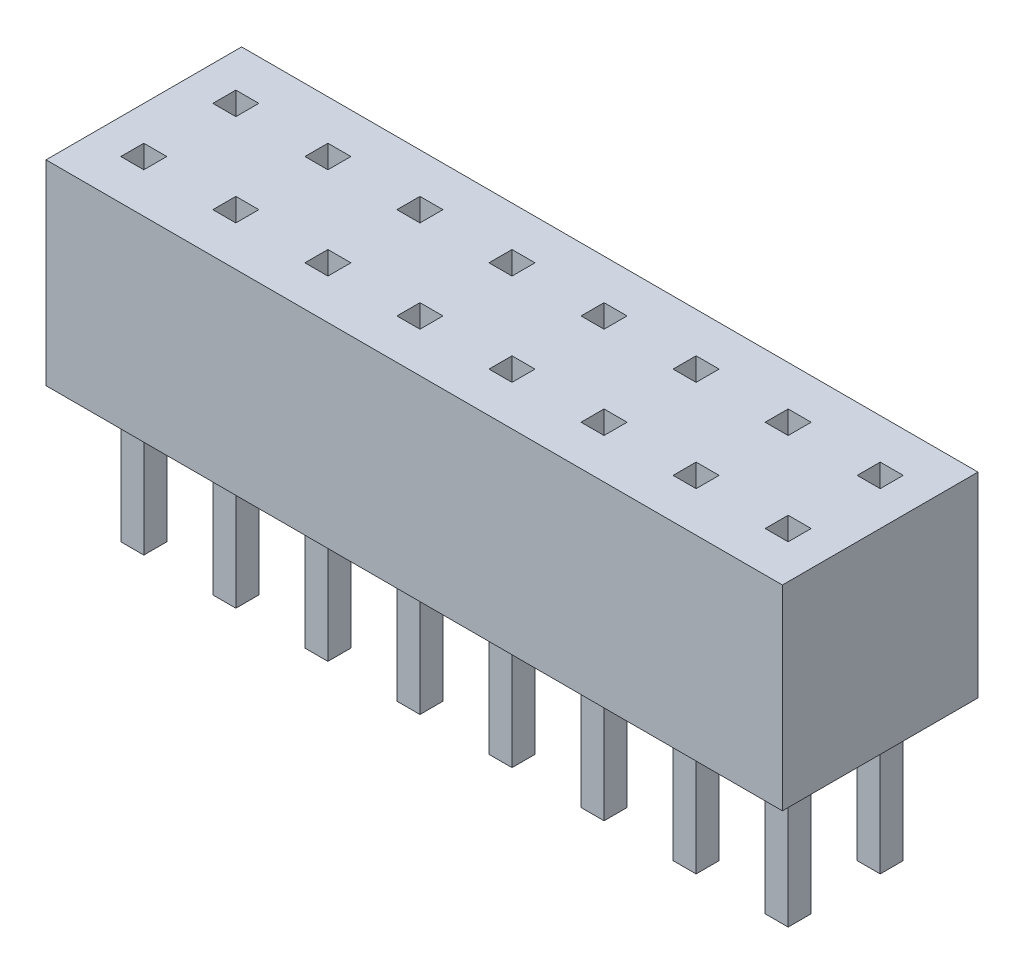
SolidWorks part; units mm, degrees
ref_plane "Front Plane" through (0, 0, 0) normal (0, 0, 1) x (1, 0, 0)
ref_plane "Top Plane" through (0, 0, 0) normal (0, 1, 0) x (1, 0, 0)
ref_plane "Right Plane" through (0, 0, 0) normal (1, 0, 0) x (0, 0, -1)
sketch "Sketch1" plane through (0, 0, 0) normal (0, 1, 0) x (1, 0, 0)
  line L1 (0, 0) -> (16, 0)
  line L2 (0, 0) -> (0, -4.25)
  line L3 (0, -4.25) -> (16, -4.25)
  line L4 (16, 0) -> (16, -4.25)
extrude "Boss-Extrude1" add sketch "Sketch1" along normal blind 4.25
sketch "Sketch3" plane through (0, 0, 0) normal (0, -1, 0) x (1, 0, 0)
  line L0 (2.75, 0.875) -> (3.25, 0.875)
  line L1 (0.75, 0.875) -> (1.25, 0.875)
  line L2 (0.75, 0.875) -> (0.75, 1.375)
  line L3 (0.75, 1.375) -> (1.25, 1.375)
  line L4 (1.25, 0.875) -> (1.25, 1.375)
  line L5 (2.75, 0.875) -> (2.75, 1.375)
  line L6 (2.75, 1.375) -> (3.25, 1.375)
  line L7 (3.25, 0.875) -> (3.25, 1.375)
  line L8 (4.75, 0.875) -> (5.25, 0.875)
  line L9 (4.75, 0.875) -> (4.75, 1.375)
  line L10 (4.75, 1.375) -> (5.25, 1.375)
  line L11 (5.25, 0.875) -> (5.25, 1.375)
  line L12 (6.75, 0.875) -> (7.25, 0.875)
  line L13 (6.75, 0.875) -> (6.75, 1.375)
  line L14 (6.75, 1.375) -> (7.25, 1.375)
  line L15 (7.25, 0.875) -> (7.25, 1.375)
  line L16 (8.75, 0.875) -> (9.25, 0.875)
  line L17 (8.75, 0.875) -> (8.75, 1.375)
  line L18 (8.75, 1.375) -> (9.25, 1.375)
  line L19 (9.25, 0.875) -> (9.25, 1.375)
  line L20 (10.75, 0.875) -> (11.25, 0.875)
  line L21 (10.75, 0.875) -> (10.75, 1.375)
  line L22 (10.75, 1.375) -> (11.25, 1.375)
  line L23 (11.25, 0.875) -> (11.25, 1.375)
  line L24 (12.75, 0.875) -> (13.25, 0.875)
  line L25 (12.75, 0.875) -> (12.75, 1.375)
  line L26 (12.75, 1.375) -> (13.25, 1.375)
  line L27 (13.25, 0.875) -> (13.25, 1.375)
  line L28 (14.75, 0.875) -> (15.25, 0.875)
  line L29 (14.75, 0.875) -> (14.75, 1.375)
  line L30 (14.75, 1.375) -> (15.25, 1.375)
  line L31 (15.25, 0.875) -> (15.25, 1.375)
  line L72 (0.75, 2.875) -> (1.25, 2.875)
  line L73 (0.75, 2.875) -> (0.75, 3.375)
  line L74 (0.75, 3.375) -> (1.25, 3.375)
  line L75 (1.25, 2.875) -> (1.25, 3.375)
  line L76 (2.75, 2.875) -> (3.25, 2.875)
  line L77 (2.75, 2.875) -> (2.75, 3.375)
  line L78 (2.75, 3.375) -> (3.25, 3.375)
  line L79 (3.25, 2.875) -> (3.25, 3.375)
  line L80 (4.75, 2.875) -> (5.25, 2.875)
  line L81 (4.75, 2.875) -> (4.75, 3.375)
  line L82 (4.75, 3.375) -> (5.25, 3.375)
  line L83 (5.25, 2.875) -> (5.25, 3.375)
  line L84 (6.75, 2.875) -> (7.25, 2.875)
  line L85 (6.75, 2.875) -> (6.75, 3.375)
  line L86 (6.75, 3.375) -> (7.25, 3.375)
  line L87 (7.25, 2.875) -> (7.25, 3.375)
  line L88 (8.75, 2.875) -> (9.25, 2.875)
  line L89 (8.75, 2.875) -> (8.75, 3.375)
  line L90 (8.75, 3.375) -> (9.25, 3.375)
  line L91 (9.25, 2.875) -> (9.25, 3.375)
  line L92 (10.75, 2.875) -> (11.25, 2.875)
  line L93 (10.75, 2.875) -> (10.75, 3.375)
  line L94 (10.75, 3.375) -> (11.25, 3.375)
  line L95 (11.25, 2.875) -> (11.25, 3.375)
  line L96 (12.75, 2.875) -> (13.25, 2.875)
  line L97 (12.75, 2.875) -> (12.75, 3.375)
  line L98 (12.75, 3.375) -> (13.25, 3.375)
  line L99 (13.25, 2.875) -> (13.25, 3.375)
  line L100 (14.75, 2.875) -> (15.25, 2.875)
  line L101 (14.75, 2.875) -> (14.75, 3.375)
  line L102 (14.75, 3.375) -> (15.25, 3.375)
  line L103 (15.25, 2.875) -> (15.25, 3.375)
  dimension "D2" = 2
  dimension "D1" = 8
extrude "Boss-Extrude2" add sketch "Sketch3" along normal blind 3
sketch "Sketch4" plane through (0, 4.25, 0) normal (0, 1, 0) x (-1, 0, 0)
  line L40 (-15.25, 0.875) -> (-14.75, 0.875)
  line L41 (-15.25, 0.875) -> (-15.25, 1.375)
  line L42 (-15.25, 1.375) -> (-14.75, 1.375)
  line L43 (-14.75, 0.875) -> (-14.75, 1.375)
  line L44 (-13.25, 0.875) -> (-12.75, 0.875)
  line L45 (-13.25, 0.875) -> (-13.25, 1.375)
  line L46 (-13.25, 1.375) -> (-12.75, 1.375)
  line L47 (-12.75, 0.875) -> (-12.75, 1.375)
  line L48 (-11.25, 0.875) -> (-10.75, 0.875)
  line L49 (-11.25, 0.875) -> (-11.25, 1.375)
  line L50 (-11.25, 1.375) -> (-10.75, 1.375)
  line L51 (-10.75, 0.875) -> (-10.75, 1.375)
  line L52 (-9.25, 0.875) -> (-8.75, 0.875)
  line L53 (-9.25, 0.875) -> (-9.25, 1.375)
  line L54 (-9.25, 1.375) -> (-8.75, 1.375)
  line L55 (-8.75, 0.875) -> (-8.75, 1.375)
  line L56 (-7.25, 0.875) -> (-6.75, 0.875)
  line L57 (-7.25, 0.875) -> (-7.25, 1.375)
  line L58 (-7.25, 1.375) -> (-6.75, 1.375)
  line L59 (-6.75, 0.875) -> (-6.75, 1.375)
  line L60 (-5.25, 0.875) -> (-4.75, 0.875)
  line L61 (-5.25, 0.875) -> (-5.25, 1.375)
  line L62 (-5.25, 1.375) -> (-4.75, 1.375)
  line L63 (-4.75, 0.875) -> (-4.75, 1.375)
  line L64 (-3.25, 0.875) -> (-2.75, 0.875)
  line L65 (-3.25, 0.875) -> (-3.25, 1.375)
  line L66 (-3.25, 1.375) -> (-2.75, 1.375)
  line L67 (-2.75, 0.875) -> (-2.75, 1.375)
  line L68 (-1.25, 0.875) -> (-0.75, 0.875)
  line L69 (-1.25, 0.875) -> (-1.25, 1.375)
  line L70 (-1.25, 1.375) -> (-0.75, 1.375)
  line L71 (-0.75, 0.875) -> (-0.75, 1.375)
  line L112 (-15.25, 2.875) -> (-14.75, 2.875)
  line L113 (-15.25, 2.875) -> (-15.25, 3.375)
  line L114 (-15.25, 3.375) -> (-14.75, 3.375)
  line L115 (-14.75, 2.875) -> (-14.75, 3.375)
  line L116 (-13.25, 2.875) -> (-12.75, 2.875)
  line L117 (-13.25, 2.875) -> (-13.25, 3.375)
  line L118 (-13.25, 3.375) -> (-12.75, 3.375)
  line L119 (-12.75, 2.875) -> (-12.75, 3.375)
  line L120 (-11.25, 2.875) -> (-10.75, 2.875)
  line L121 (-11.25, 2.875) -> (-11.25, 3.375)
  line L122 (-11.25, 3.375) -> (-10.75, 3.375)
  line L123 (-10.75, 2.875) -> (-10.75, 3.375)
  line L124 (-9.25, 2.875) -> (-8.75, 2.875)
  line L125 (-9.25, 2.875) -> (-9.25, 3.375)
  line L126 (-9.25, 3.375) -> (-8.75, 3.375)
  line L127 (-8.75, 2.875) -> (-8.75, 3.375)
  line L128 (-7.25, 2.875) -> (-6.75, 2.875)
  line L129 (-7.25, 2.875) -> (-7.25, 3.375)
  line L130 (-7.25, 3.375) -> (-6.75, 3.375)
  line L131 (-6.75, 2.875) -> (-6.75, 3.375)
  line L132 (-5.25, 2.875) -> (-4.75, 2.875)
  line L133 (-5.25, 2.875) -> (-5.25, 3.375)
  line L134 (-5.25, 3.375) -> (-4.75, 3.375)
  line L135 (-4.75, 2.875) -> (-4.75, 3.375)
  line L137 (-3.25, 2.875) -> (-2.75, 2.875)
  line L138 (-3.25, 2.875) -> (-3.25, 3.375)
  line L139 (-3.25, 3.375) -> (-2.75, 3.375)
  line L140 (-2.75, 2.875) -> (-2.75, 3.375)
  line L141 (-1.25, 2.875) -> (-0.75, 2.875)
  line L142 (-1.25, 2.875) -> (-1.25, 3.375)
  line L143 (-1.25, 3.375) -> (-0.75, 3.375)
  line L144 (-0.75, 2.875) -> (-0.75, 3.375)
  line L145 (-33.25, 0.875) -> (-32.75, 0.875)
  line L146 (-35.25, 0.875) -> (-34.75, 0.875)
  line L147 (-35.25, 0.875) -> (-35.25, 1.375)
  line L148 (-35.25, 1.375) -> (-34.75, 1.375)
  line L149 (-34.75, 0.875) -> (-34.75, 1.375)
  line L150 (-33.25, 0.875) -> (-33.25, 1.375)
  line L151 (-33.25, 1.375) -> (-32.75, 1.375)
  line L152 (-32.75, 0.875) -> (-32.75, 1.375)
  line L153 (-31.25, 0.875) -> (-30.75, 0.875)
  line L154 (-31.25, 0.875) -> (-31.25, 1.375)
  line L155 (-31.25, 1.375) -> (-30.75, 1.375)
  line L156 (-30.75, 0.875) -> (-30.75, 1.375)
  line L157 (-29.25, 0.875) -> (-28.75, 0.875)
  line L158 (-29.25, 0.875) -> (-29.25, 1.375)
  line L159 (-29.25, 1.375) -> (-28.75, 1.375)
  line L160 (-28.75, 0.875) -> (-28.75, 1.375)
  line L161 (-27.25, 0.875) -> (-26.75, 0.875)
  line L162 (-27.25, 0.875) -> (-27.25, 1.375)
  line L163 (-27.25, 1.375) -> (-26.75, 1.375)
  line L164 (-26.75, 0.875) -> (-26.75, 1.375)
  line L165 (-25.25, 0.875) -> (-24.75, 0.875)
  line L166 (-25.25, 0.875) -> (-25.25, 1.375)
  line L167 (-25.25, 1.375) -> (-24.75, 1.375)
  line L168 (-24.75, 0.875) -> (-24.75, 1.375)
  line L169 (-23.25, 0.875) -> (-22.75, 0.875)
  line L170 (-23.25, 0.875) -> (-23.25, 1.375)
  line L171 (-23.25, 1.375) -> (-22.75, 1.375)
  line L172 (-22.75, 0.875) -> (-22.75, 1.375)
  line L173 (-21.25, 0.875) -> (-20.75, 0.875)
  line L174 (-21.25, 0.875) -> (-21.25, 1.375)
  line L175 (-21.25, 1.375) -> (-20.75, 1.375)
  line L176 (-20.75, 0.875) -> (-20.75, 1.375)
  line L177 (-19.25, 0.875) -> (-18.75, 0.875)
  line L178 (-19.25, 0.875) -> (-19.25, 1.375)
  line L179 (-19.25, 1.375) -> (-18.75, 1.375)
  line L180 (-18.75, 0.875) -> (-18.75, 1.375)
  line L181 (-17.25, 0.875) -> (-16.75, 0.875)
  line L182 (-17.25, 0.875) -> (-17.25, 1.375)
  line L183 (-17.25, 1.375) -> (-16.75, 1.375)
  line L184 (-16.75, 0.875) -> (-16.75, 1.375)
  line L185 (-35.25, 2.875) -> (-34.75, 2.875)
  line L186 (-35.25, 2.875) -> (-35.25, 3.375)
  line L187 (-35.25, 3.375) -> (-34.75, 3.375)
  line L188 (-34.75, 2.875) -> (-34.75, 3.375)
  line L189 (-33.25, 2.875) -> (-32.75, 2.875)
  line L190 (-33.25, 2.875) -> (-33.25, 3.375)
  line L191 (-33.25, 3.375) -> (-32.75, 3.375)
  line L192 (-32.75, 2.875) -> (-32.75, 3.375)
  line L193 (-31.25, 2.875) -> (-30.75, 2.875)
  line L194 (-31.25, 2.875) -> (-31.25, 3.375)
  line L195 (-31.25, 3.375) -> (-30.75, 3.375)
  line L196 (-30.75, 2.875) -> (-30.75, 3.375)
  line L197 (-29.25, 2.875) -> (-28.75, 2.875)
  line L198 (-29.25, 2.875) -> (-29.25, 3.375)
  line L199 (-29.25, 3.375) -> (-28.75, 3.375)
  line L200 (-28.75, 2.875) -> (-28.75, 3.375)
  line L201 (-27.25, 2.875) -> (-26.75, 2.875)
  line L202 (-27.25, 2.875) -> (-27.25, 3.375)
  line L203 (-27.25, 3.375) -> (-26.75, 3.375)
  line L204 (-26.75, 2.875) -> (-26.75, 3.375)
  line L205 (-25.25, 2.875) -> (-24.75, 2.875)
  line L206 (-25.25, 2.875) -> (-25.25, 3.375)
  line L207 (-25.25, 3.375) -> (-24.75, 3.375)
  line L208 (-24.75, 2.875) -> (-24.75, 3.375)
  line L209 (-23.25, 2.875) -> (-22.75, 2.875)
  line L210 (-23.25, 2.875) -> (-23.25, 3.375)
  line L211 (-23.25, 3.375) -> (-22.75, 3.375)
  line L212 (-22.75, 2.875) -> (-22.75, 3.375)
  line L213 (-21.25, 2.875) -> (-20.75, 2.875)
  line L214 (-21.25, 2.875) -> (-21.25, 3.375)
  line L215 (-21.25, 3.375) -> (-20.75, 3.375)
  line L216 (-20.75, 2.875) -> (-20.75, 3.375)
  line L217 (-19.25, 2.875) -> (-18.75, 2.875)
  line L218 (-19.25, 2.875) -> (-19.25, 3.375)
  line L219 (-19.25, 3.375) -> (-18.75, 3.375)
  line L220 (-18.75, 2.875) -> (-18.75, 3.375)
  line L221 (-17.25, 2.875) -> (-16.75, 2.875)
  line L222 (-17.25, 2.875) -> (-17.25, 3.375)
  line L223 (-17.25, 3.375) -> (-16.75, 3.375)
  line L224 (-16.75, 2.875) -> (-16.75, 3.375)
  dimension "D2" = 17
extrude "Cut-Extrude1" cut sketch "Sketch4" against normal blind 4
ref_plane "Plane1" through (5.0625, 0, 5.0625) normal (-0.7071, 0, -0.7071) x (-0.7071, 0, 0.7071)
ref_plane "Plane2" through (2.9375, 0, -2.9375) normal (0.7071, 0, -0.7071) x (-0.7071, 0, -0.7071)
ref_axis "Axis1" through (8, 0.05, 2.125) along (0, 1, 0)
